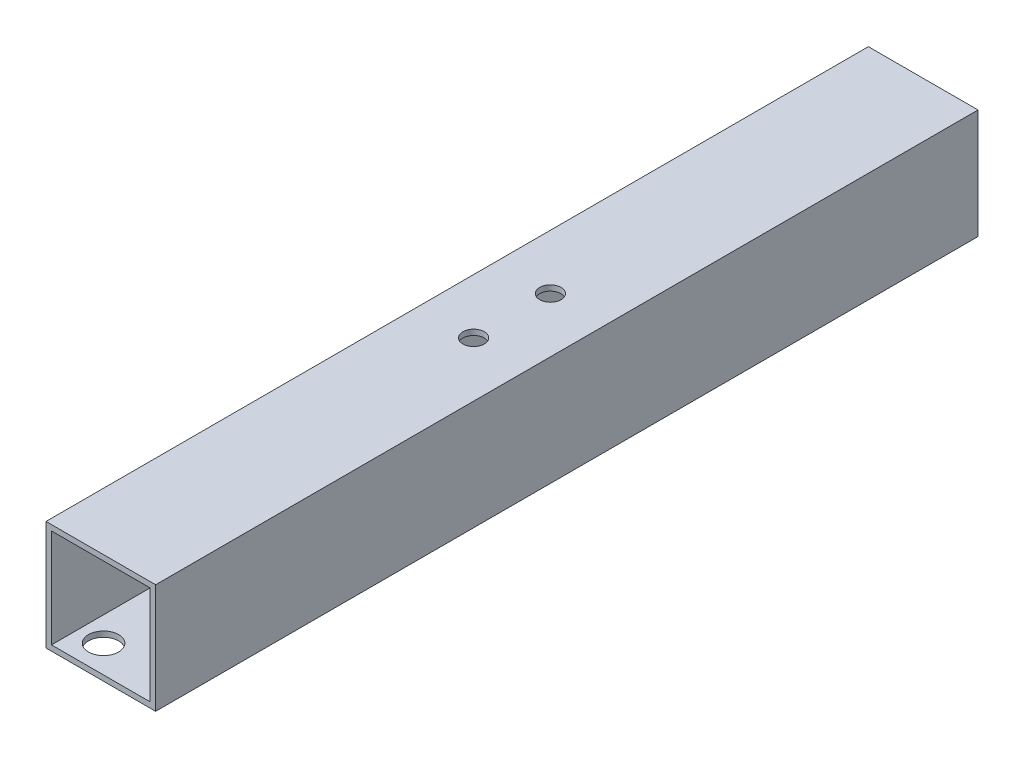
SolidWorks part; units mm, degrees
material "1060 合金"
ref_plane "前视基准面" through (0, 0, 0) normal (0, 0, 1) x (1, 0, 0)
ref_plane "上视基准面" through (0, 0, 0) normal (0, 1, 0) x (1, 0, 0)
ref_plane "右视基准面" through (0, 0, 0) normal (1, 0, 0) x (0, 0, -1)
other "Configuration Table"
sketch "草图1" plane through (0, 0, 0) normal (0, 0, 1) x (1, 0, 0)
  line L1 (0, 0) -> (20, 0)
  line L2 (0, 0) -> (0, -20)
  line L3 (0, -20) -> (20, -20)
  line L4 (20, 0) -> (20, -20)
  dimension "D1" = 20
  dimension "D2" = 20
extrude "拉伸-薄壁1" add sketch "草图1" along normal blind 150 thin thin type one direction reverse wall 1
sketch "草图2" plane through (0, -20, 0) normal (0, -1, 0) x (1, 0, 0)
  circle A1 centre (7.5, 825) radius 2.6
  circle A2 centre (7.5, 825) radius 2.6
  dimension "D1" = 0
extrude "切除-拉伸1" [suppressed] cut sketch "草图2" against normal up to next
sketch "草图3" plane through (0, -20, 0) normal (0, -1, 0) x (1, 0, 0)
  line L0 (20, 150) -> (20, 0) construction
  line L3 (0, 0) -> (20, 0) construction
  circle A0 centre (10, 82) radius 1.95
  circle A1 centre (10, 68) radius 1.95
  dimension "D1" = 3.9
  dimension "D4" = 3.9
  dimension "D2" = 10
  dimension "D3" = 14
  dimension "D5" = 68
  dimension "D6" = 10
extrude "切除-拉伸2" cut sketch "草图3" against normal through all
sketch "草图4" plane through (0, -20, 0) normal (0, -1, 0) x (1, 0, 0)
  line L0 (0, 150) -> (20, 150) construction
  line L1 (0, 150) -> (0, 0) construction
  circle A0 centre (5.5, 145) radius 2.75
  circle A1 centre (5.5, 5) radius 2.75
  dimension "D2" = 5.5
  dimension "D1" = 5
  dimension "D3" = 5.5
  dimension "D4" = 2
extrude "切除-拉伸3" cut sketch "草图4" against normal up to next
